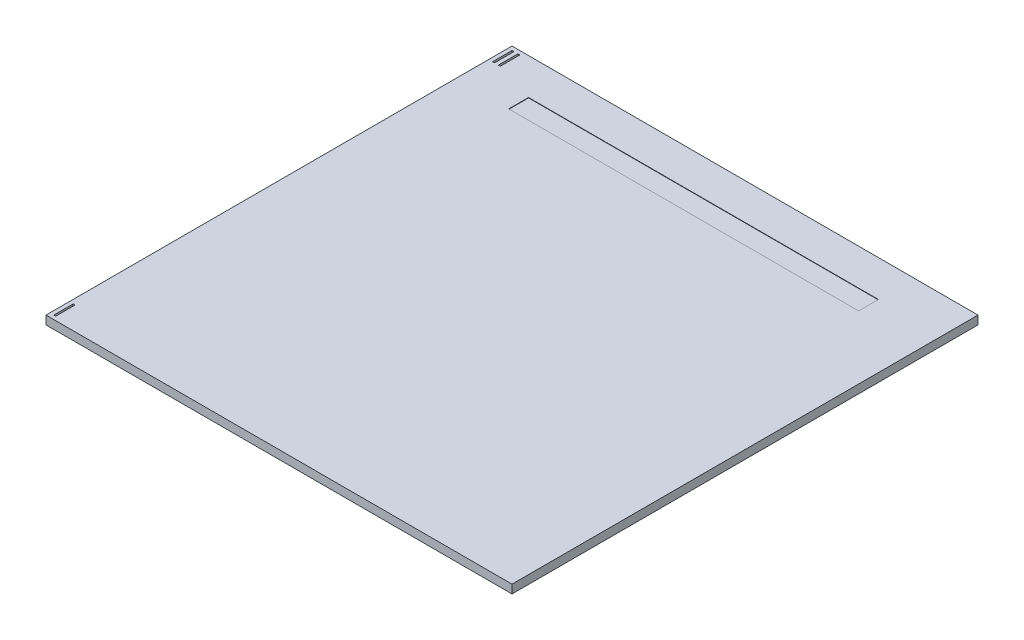
SolidWorks part; units mm, degrees
material "Acrylic (Medium-high impact)"
ref_plane "Front Plane" through (0, 0, 0) normal (0, 0, 1) x (1, 0, 0)
ref_plane "Top Plane" through (0, 0, 0) normal (0, 1, 0) x (1, 0, 0)
ref_plane "Right Plane" through (0, 0, 0) normal (1, 0, 0) x (0, 0, -1)
sketch "Sketch2" plane through (0, 0, 0) normal (0, 1, 0) x (1, 0, 0)
  line L1 (0, 0) -> (304.8, 0)
  line L2 (0, 0) -> (0, 304.8)
  line L3 (0, 304.8) -> (304.8, 304.8)
  line L4 (304.8, 0) -> (304.8, 304.8)
  dimension "D1" = 304.8
  dimension "D2" = 304.8
extrude "Boss-Extrude1" add sketch "Sketch2" along normal blind 5.588
sketch "Sketch4" plane through (0, 5.588, 0) normal (0, 1, 0) x (1, 0, 0)
  line L0 (0, 304.8) -> (0, 0) construction
  line L1 (2.54, 2.54) -> (3.81, 2.54)
  line L2 (2.54, 2.54) -> (2.54, 15.24)
  line L3 (2.54, 15.24) -> (3.81, 15.24)
  line L4 (3.81, 2.54) -> (3.81, 15.24)
  line L5 (2.54, 302.26) -> (3.81, 302.26)
  line L6 (2.54, 302.26) -> (2.54, 289.56)
  line L7 (2.54, 289.56) -> (3.81, 289.56)
  line L8 (3.81, 302.26) -> (3.81, 289.56)
  line L9 (6.35, 302.26) -> (7.62, 302.26)
  line L10 (6.35, 302.26) -> (6.35, 289.56)
  line L11 (6.35, 289.56) -> (7.62, 289.56)
  line L12 (7.62, 302.26) -> (7.62, 289.56)
  line L13 (304.8, 304.8) -> (0, 304.8) construction
  line L14 (0, 0) -> (304.8, 0) construction
  dimension "D1" = 12.7
  dimension "D2" = 1.27
  dimension "D3" = 2.54
  dimension "D4" = 2.54
  dimension "D5" = 2.54
  dimension "D6" = 2.54
  dimension "D7" = 2.54
extrude "Cut-Extrude1" cut sketch "Sketch4" against normal through all
sketch "Sketch5" plane through (0, 5.588, 0) normal (0, 1, 0) x (1, 0, 0)
  line L0 (0, 304.8) -> (0, 0) construction
  line L1 (34.5465, 268.1122) -> (263.4005, 268.1122)
  line L2 (34.5465, 268.1122) -> (34.5465, 281.0662)
  line L3 (34.5465, 281.0662) -> (263.4005, 281.0662)
  line L4 (263.4005, 268.1122) -> (263.4005, 281.0662)
  line L5 (304.8, 0) -> (304.8, 304.8) construction
  line L6 (304.8, 304.8) -> (0, 304.8) construction
  dimension "D1" = 34.5465
  dimension "D2" = 41.3995
  dimension "D3" = 23.7338
  dimension "D4" = 12.954
extrude "Cut-Extrude2" cut sketch "Sketch5" against normal blind 0.254
